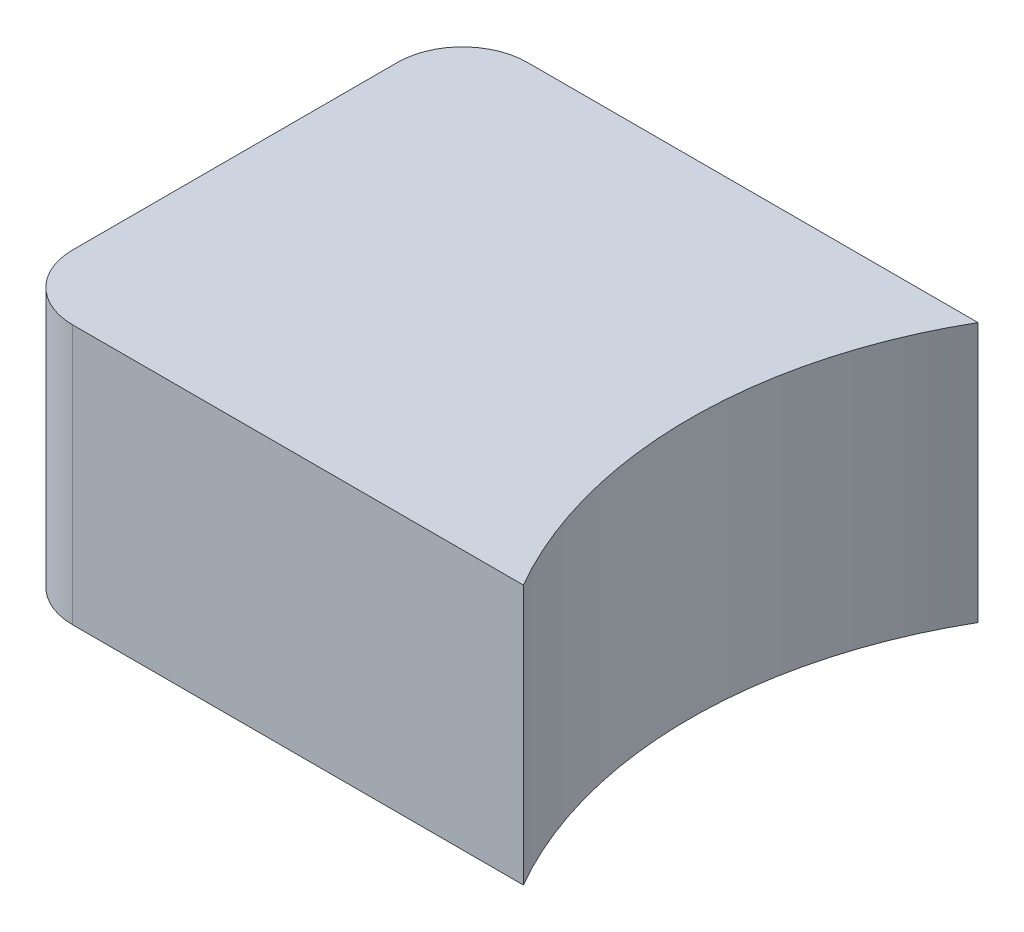
SolidWorks part; units mm, degrees
ref_plane "Front Plane" through (0, 0, 0) normal (0, 0, 1) x (1, 0, 0)
ref_plane "Top Plane" through (0, 0, 0) normal (0, 1, 0) x (1, 0, 0)
ref_plane "Right Plane" through (0, 0, 0) normal (1, 0, 0) x (0, 0, -1)
body saved out of another part "Stock-HoldingPinMP_Diego-1" rebuild error yes
sketch "Sketch1" plane through (-3.1, 0, 0) normal (1, 0, 0) x (0, 0, -1)
  line L0 (1.6468, 74.009) -> (1.6468, -23.7773) construction
  line L1 (-2.5275, 86.2227) -> (-2.5275, -23.7773) construction
  line L2 (1.6468, 100.2227) -> (1.6468, -23.7773)
  line L3 (-2.5275, 111.2227) -> (-2.5275, -23.7773)
  line L4 (-2.5275, -23.7773) -> (-2.5275, -48)
  line L5 (-1.2, -48) -> (-6.0522, -48) construction
  line L6 (1.6468, -23.7773) -> (1.6468, -48)
  dimension "D1" = 135
  dimension "D2" = 11
extrude "Cut-Extrude-Thin1" cut sketch "Sketch1" against normal blind 1.9 thin rebuild error yes thin type mid plane wall 2.5
sketch "Sketch2" plane through (0, 0, 0) normal (0, 1, 0) x (1, 0, 0)
  line L1 (-14, -3.5) -> (-6.0622, -3.5)
  line L2 (-14, -3.5) -> (-14, 3.5)
  line L3 (-14, 3.5) -> (-6.0622, 3.5)
  line L5 (-14, 0) -> (-7, 0) construction
  arc A3 (-6.226, 3.1996) -> (-5.7446, -4) centre (0, 0) ccw construction
  arc A4 (-6.0622, 3.5) -> (-6.0622, -3.5) centre (0, 0) ccw
  dimension "D1" = 7
  dimension "D2" = 7
extrude "Boss-Extrude1" add sketch "Sketch2" along normal blind 4 from offset 10 offset against normal yes
fillet "Fillet1" radius 1 2 edges at (-14, -8, 3.5) (-14, -8, -3.5)
sketch "Sketch3" plane through (0, -10, 0) normal (0, -1, 0) x (1, 0, 0)
  line L0 (6.6, 0) -> (-6.6, 0) construction
  line L1 (0, -6.6) -> (0, 6.6) construction
  circle A0 centre (-10.5, 0) radius 3
  dimension "D2" = 6
  dimension "D1" = 10.5
extrude "Cut-Extrude1" cut sketch "Sketch3" against normal blind 1.5
chamfer "Chamfer1" distance 0.3 angle 45 1 edges at (-10.5, -10, -3)
sketch "Sketch4" plane through (-3.1, 0, 0) normal (1, 0, 0) x (0, 0, -1)
  line L1 (-1.2775, 95.2738) -> (-5.2775, 95.2738)
  line L2 (-1.2775, 95.2738) -> (-1.2775, 86.0466)
  line L3 (-1.2775, 86.0466) -> (-5.2775, 86.0466)
  line L4 (-5.2775, 95.2738) -> (-5.2775, 86.0466)
  spline S0 degree 2 poles (-4, 86.2227) (-7, 86.2227) (-7, 83.2227) knots 0 0 0 1 1 1 weights 1 1 1 construction
  dimension "D1" = 4
extrude "Cut-Extrude2" cut sketch "Sketch4" against normal up to surface (1.9 mm away) rebuild error yes
fillet "Fillet4" radius 0.5 rebuild error yes
fillet "Fillet5" radius 0.7 rebuild error yes
